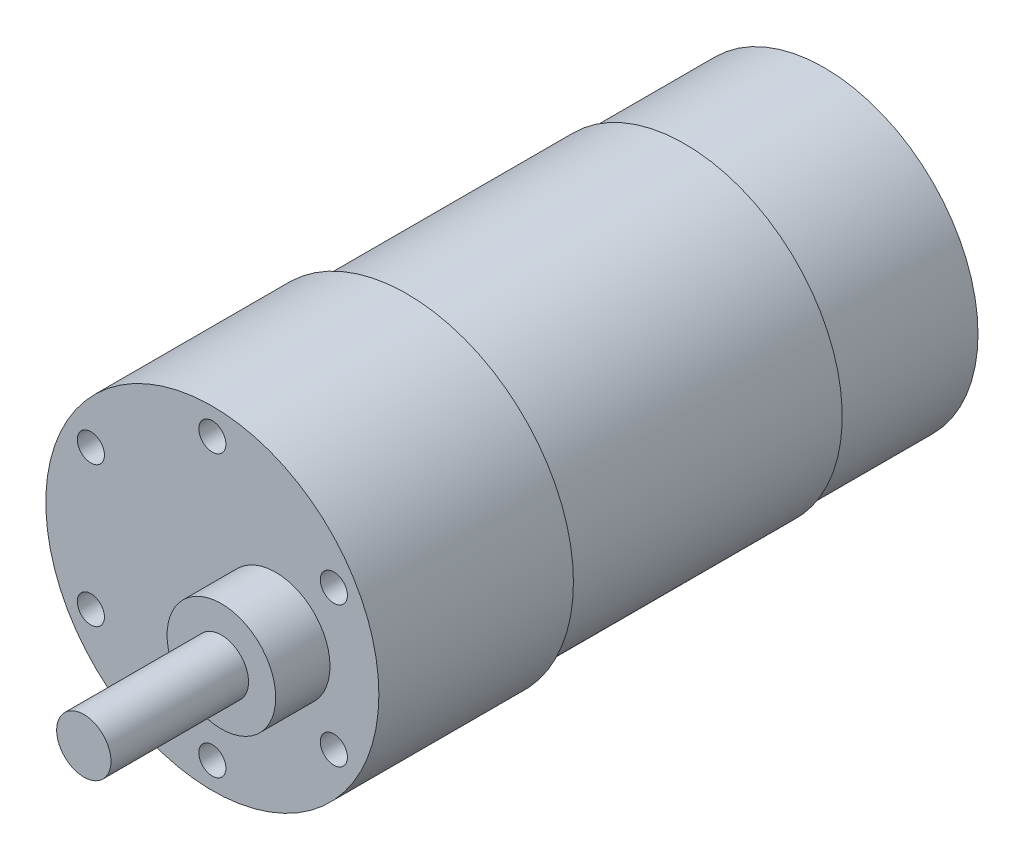
SolidWorks part; units mm, degrees
ref_plane "정면" through (0, 0, 0) normal (0, 0, 1) x (1, 0, 0)
ref_plane "윗면" through (0, 0, 0) normal (0, 1, 0) x (1, 0, 0)
ref_plane "우측면" through (0, 0, 0) normal (1, 0, 0) x (0, 0, -1)
sketch "스케치1" plane through (0, 0, 0) normal (0, 0, 1) x (1, 0, 0)
  circle A0 centre (0, 0) radius 18.4
  circle A1 centre (0, 0) radius 15.5 construction
  circle A2 centre (0, 15.5) radius 1.5
  circle A3 centre (13.4234, 7.75) radius 1.5
  circle A4 centre (13.4234, -7.75) radius 1.5
  circle A5 centre (0, -15.5) radius 1.5
  circle A6 centre (-13.4234, -7.75) radius 1.5
  circle A7 centre (-13.4234, 7.75) radius 1.5
  circle A8 centre (7, 0) radius 6
  circle A9 centre (7, 0) radius 3
  point P19 (0, 0)
  dimension "D1" = 36.8
  dimension "D2" = 31
  dimension "D3" = 3
  dimension "D6" = 0
  dimension "D7" = 12
  dimension "D8" = 6
  dimension "D5" = 7
  dimension "D4" = 6
extrude "보스-돌출1" add sketch "스케치1" against normal blind 21.5 contours A0
extrude "보스-돌출2" add sketch "스케치1<3>" along normal blind 6 contours A8
sketch "스케치1<3>" plane through (0, 0, 0) normal (0, 0, 1) x (1, 0, 0) same geometry as "스케치1"
extrude "보스-돌출3" add sketch "스케치1<4>" along normal blind 21.2 contours A9
sketch "스케치1<4>" plane through (0, 0, 0) normal (0, 0, 1) x (1, 0, 0) same geometry as "스케치1"
sketch "스케치2" plane through (0, 0, -21.5) normal (0, 0, -1) x (-1, 0, 0)
  circle A0 centre (0, 0) radius 17.4
  circle A1 centre (0, 0) radius 17
  dimension "D1" = 34.8
  dimension "D2" = 34
extrude "보스-돌출4" add sketch "스케치2" along normal blind 30.7 contours A0
extrude "보스-돌출5" add sketch "스케치2<3>" along normal blind 15.4 from surface contours A1 starting at face at (-17.4, 0, -52.2)
sketch "스케치2<3>" plane through (0, 0, -21.5) normal (0, 0, -1) x (-1, 0, 0) same geometry as "스케치2"
extrude "컷-돌출1" cut sketch "스케치1<5>" against normal blind 5 contours A6 | A7 | A2 | A3 | A4 | A5 region at (0, 15.5, 0) region at (13.4234, 7.75, 0) region at (13.4234, -7.75, 0) region at (-13.4234, -7.75, 0) region at (-13.4234, 7.75, 0)
sketch "스케치1<5>" plane through (0, 0, 0) normal (0, 0, 1) x (1, 0, 0) same geometry as "스케치1"
